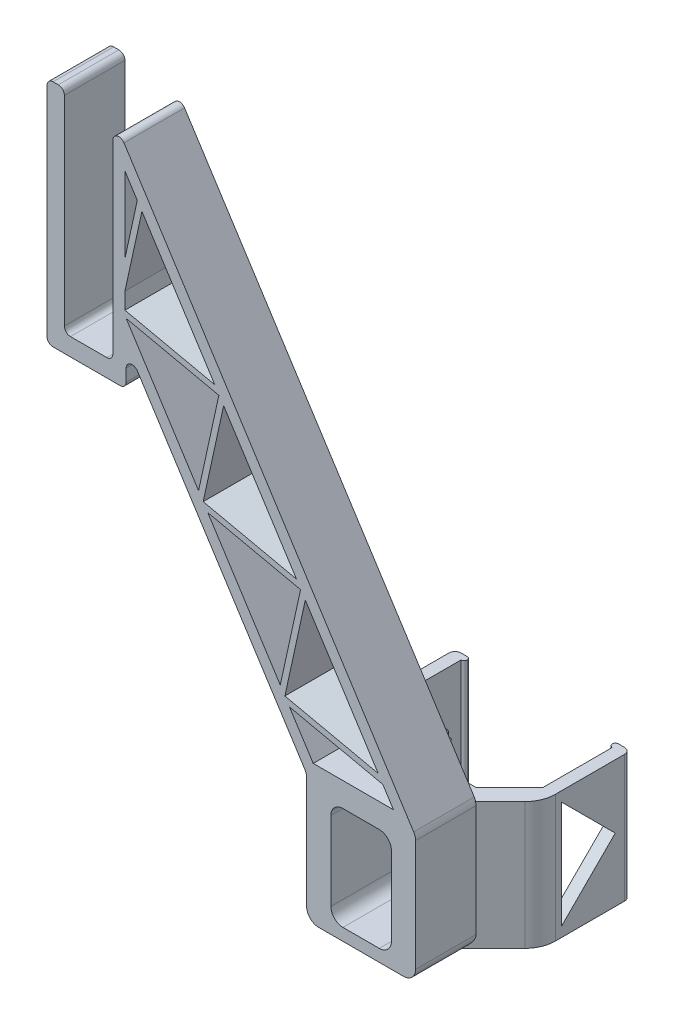
SolidWorks part; units mm, degrees
ref_plane "Front Plane" through (0, 0, 0) normal (0, 0, 1) x (1, 0, 0)
ref_plane "Top Plane" through (0, 0, 0) normal (0, 1, 0) x (1, 0, 0)
ref_plane "Right Plane" through (0, 0, 0) normal (1, 0, 0) x (0, 0, -1)
sketch "Sketch3" plane through (0, 0, 0) normal (0, 1, 0) x (1, 0, 0)
  line L0 (0, 0) -> (14, 0)
  line L1 (14, 0) -> (19.5, 5.5)
  line L2 (19.5, 5.5) -> (19.5, 18)
  line L3 (19.5, 18) -> (21.5, 18)
  line L4 (21.5, 18) -> (21.5, -2)
  line L5 (21.5, -2) -> (-7.5, -2)
  line L6 (-7.5, -2) -> (-7.5, 18)
  line L7 (-7.5, 18) -> (-5.5, 18)
  line L8 (-5.5, 18) -> (-5.5, 5.5)
  line L9 (-5.5, 5.5) -> (0, 0)
  line L10 (7, 0) -> (7, -2)
  line L11 (7, -2) -> (-2, -2)
  line L12 (7, -2) -> (16, -2)
  line L13 (16, -2) -> (21.5, 3.5)
  line L14 (-2, -2) -> (-7.5, 3.5)
  dimension "D1" = 135
  dimension "D2" = 135
  dimension "D3" = 14
  dimension "D4" = 12.5
  dimension "D5" = 12.5
  dimension "D6" = 2
  dimension "D7" = 2
  dimension "D8" = 2
  dimension "D9" = 20
  dimension "D10" = 20
  dimension "D11" = 135
  dimension "D12" = 135
  dimension "D13" = 9
  dimension "D14" = 9
extrude "Boss-Extrude2" add sketch "Sketch3" along normal blind 21 contours L10 L0 L9 L8 L7 L6 L5 | L0 L10 L5 L4 L3 L2 L1 region at (3.5, 0, 0.247) region at (10.5, 0, 0.247)
fillet "Fillet1" radius 5 2 edges at (21.5, 10.5, -3.5) (-7.5, 10.5, -3.5)
sketch "Sketch4" plane through (0, 21, 0) normal (0, 1, 0) x (1, 0, 0)
  line L0 (-5.5, 18) -> (-5.5, 5.5) construction
  circle A0 centre (-5.5, 17.5) radius 0.5
  dimension "D1" = 1
  dimension "D2" = 0.5
extrude "Boss-Extrude3" add sketch "Sketch4" against normal blind 21
sketch "Sketch5" plane through (0, 21, 0) normal (0, 1, 0) x (1, 0, 0)
  line L0 (19.5, 5.5) -> (19.5, 18) construction
  circle A0 centre (19.5, 17.5) radius 0.5
  dimension "D1" = 1
  dimension "D2" = 0.5
extrude "Boss-Extrude4" add sketch "Sketch5" against normal blind 21
fillet "Fillet2" radius 1 2 edges at (21.5, 10.5, -18) (-7.5, 10.5, -18)
sketch "Sketch6" plane through (0, 21, 0) normal (0, 1, 0) x (1, 0, 0)
  line L0 (16, -2) -> (-2, -2) construction
  line L1 (0, 0) -> (14, 0) construction
  line L2 (1.4514, 5) -> (1.4514, 0)
  line L3 (1.4514, 5) -> (4.4514, 5)
  line L4 (4.4514, 5) -> (4.4514, 0)
  line L7 (1.4514, 0) -> (1.4514, -2)
  line L8 (1.4514, -2) -> (4.4514, -2)
  line L9 (4.4514, 0) -> (4.4514, -2)
  dimension "D1" = 5
  dimension "D2" = 3
extrude "Boss-Extrude5" add sketch "Sketch6" along normal blind 1.5
fillet "Fillet3" radius 1 1 edges at (2.9514, 22.5, 2)
fillet "Fillet4" radius 1 1 edges at (2.9514, 22.5, -5)
sketch "Sketch7" plane through (1.4514, 0, 0) normal (-1, 0, 0) x (0, 0, 1)
  line L0 (-5, 21) -> (0, 21) construction
  circle A0 centre (-4.5, 21) radius 0.5
  dimension "D1" = 1
  dimension "D2" = 0.5
extrude "Boss-Extrude6" add sketch "Sketch7" against normal up to surface (3 mm away) up to face at (4.4514, 21.6663, -1.1429)
sketch "Sketch8" plane through (0, 0, 0) normal (0, -1, 0) x (1, 0, 0)
  line L0 (16, 2) -> (-2, 2) construction
  line L1 (1.4514, 2) -> (4.4514, 2)
  line L2 (1.4514, 2) -> (1.4514, -5)
  line L3 (1.4514, -5) -> (4.4514, -5)
  line L4 (4.4514, 2) -> (4.4514, -5)
extrude "Boss-Extrude7" add sketch "Sketch8" along normal blind 1.5
fillet "Fillet5" radius 1 2 edges at (2.9514, -1.5, -5) (2.9514, -1.5, 2)
sketch "Sketch9" plane through (4.4514, 0, 0) normal (1, 0, 0) x (0, 0, -1)
  line L0 (5, 0) -> (0, 0) construction
  circle A0 centre (4.5, 0) radius 0.5
  dimension "D1" = 1
  dimension "D2" = 0.5
extrude "Boss-Extrude8" add sketch "Sketch9" against normal up to surface (3 mm away) up to face at (1.4514, -0.6663, -1.1429)
sketch "Sketch10" plane through (0, 0, 0) normal (0, 0, -1) x (-1, 0, 0)
  line L0 (-4.4514, 21) -> (-14, 21) construction
  line L1 (-2, 19) -> (-12, 19)
  line L2 (-2, 19) -> (-2, 2)
  line L3 (-2, 2) -> (-12, 2)
  line L4 (-12, 19) -> (-12, 2)
  line L5 (-4.4514, 0) -> (-14, 0) construction
  line L6 (-14, 21) -> (-14, 0) construction
  line L7 (0, 21) -> (0, 0) construction
  point P4 (-9.2257, 21)
  dimension "D1" = 2
  dimension "D2" = 2
  dimension "D3" = 2
  dimension "D4" = 2
extrude "Cut-Extrude1" cut sketch "Sketch10" against normal through all
sketch "Sketch11" plane through (-7.5, 0, 0) normal (-1, 0, 0) x (0, 0, 1)
  line L0 (-6.5711, 19.4) -> (-6.5711, 1.6048)
  line L1 (-6.5711, 1.6048) -> (-15.4687, 10.5024)
  line L2 (-15.4687, 10.5024) -> (-6.5711, 19.4)
  line L3 (-5.5711, 0) -> (-17, 0) construction
  line L4 (-5.5711, 21) -> (-17, 21) construction
  line L5 (-5.5711, 0) -> (-5.5711, 21) construction
  dimension "D1" = 90
  dimension "D2" = 1.6048
  dimension "D3" = 1.6
  dimension "D4" = 1
extrude "Cut-Extrude2" cut sketch "Sketch11" against normal through all
sketch "Sketch12" plane through (0, 0, 2) normal (0, 0, 1) x (1, 0, 0)
  line L1 (16, 21) -> (-2, 21)
  line L2 (16, 21) -> (16, 0)
  line L3 (16, 0) -> (-2, 0)
  line L4 (-2, 21) -> (-2, 0)
  line L5 (12, 19) -> (2, 19)
  line L6 (12, 19) -> (12, 2)
  line L7 (12, 2) -> (2, 2)
  line L8 (2, 19) -> (2, 2)
extrude "Boss-Extrude9" add sketch "Sketch12" along normal blind 10
sketch "Sketch13" plane through (0, 0, 12) normal (0, 0, 1) x (1, 0, 0)
  line L0 (16, 21) -> (-34, 99)
  line L1 (-2, 21) -> (-34, 70.9218)
  line L2 (-34, 70.9218) -> (-34, 99)
  line L4 (16, 21) -> (-2, 21) construction
  line L5 (16, 21) -> (-2, 21)
  line L6 (-0.9064, 23) -> (-32, 71.5077)
  line L7 (-32, 71.5077) -> (-32, 92.174)
  line L8 (12.3423, 23) -> (-32, 92.174)
  line L9 (12.3423, 23) -> (-0.9064, 23)
  dimension "D1" = 78
  dimension "D2" = 50
  dimension "D3" = 122.661
  dimension "D4" = 122.66
  dimension "D5" = 28.0782
  dimension "D6" = 2
extrude "Boss-Extrude10" add sketch "Sketch13" against normal blind 10
sketch "Sketch14" plane through (0, 0, 12) normal (0, 0, 1) x (1, 0, 0)
  line L0 (10.5854, 25.7408) -> (-4.8239, 29.1116)
  line L1 (12.3423, 23) -> (-32, 92.174) construction
  line L2 (-32, 71.5077) -> (-0.9064, 23) construction
  line L3 (-4.8239, 29.1116) -> (-6.7486, 29.5326)
  line L4 (10.7991, 26.7177) -> (-4.6102, 30.0885)
  line L5 (-4.6102, 30.0885) -> (-6.5349, 30.5095)
  line L6 (10.5854, 25.7408) -> (10.7991, 26.7177)
  line L7 (-6.5349, 30.5095) -> (-6.7486, 29.5326)
  dimension "D1" = 45
  dimension "D2" = 1
extrude "Boss-Extrude14" add sketch "Sketch14" against normal blind 10
sketch "Sketch16" plane through (0, 0, 12) normal (0, 0, 1) x (1, 0, 0)
  line L0 (-5.5871, 30.3022) -> (-2.2163, 45.7115)
  line L1 (9.8222, 26.9314) -> (-32, 92.174) construction
  line L2 (-2.2163, 45.7115) -> (-2.0256, 46.5834)
  line L3 (9.8222, 26.9314) -> (-5.5871, 30.3022) construction
  line L4 (-2.0256, 46.5834) -> (-1.7752, 47.7281)
  line L5 (-6.564, 30.5159) -> (-3.1932, 45.9252)
  line L6 (-3.1932, 45.9252) -> (-3.0025, 46.7971)
  line L7 (-3.0025, 46.7971) -> (-2.7521, 47.9418)
  line L8 (-5.5871, 30.3022) -> (-6.564, 30.5159)
  line L9 (-2.7521, 47.9418) -> (-1.7752, 47.7281)
  dimension "D1" = 90
  dimension "D2" = 1
extrude "Boss-Extrude15" add sketch "Sketch16" against normal blind 10
pattern_linear "LPattern1" count 3 spacing 25 along (-0.5397, 0.8419, 0) of "Boss-Extrude14", "Boss-Extrude15"
sketch "Sketch17" plane through (0, 0, 12) normal (0, 0, 1) x (1, 0, 0)
  line L0 (-34, 99) -> (-34, 70.9218) construction
  line L1 (-42, 64) -> (-44.8755, 64)
  line L2 (-42, 64) -> (-42, 99)
  line L3 (-42, 99) -> (-44.8755, 99)
  line L4 (-44.8755, 64) -> (-44.8755, 99)
  dimension "D1" = 8
  dimension "D2" = 35
  dimension "D3" = 0
extrude "Boss-Extrude16" add sketch "Sketch17" against normal blind 10 separate body
sketch "Sketch18" plane through (0, 0, 12) normal (0, 0, 1) x (1, 0, 0)
  line L0 (-34, 64) -> (-34, 71.0352)
  line L1 (-34, 71.0352) -> (-31.8062, 71.2053)
  line L2 (-42, 64) -> (-44.8755, 64)
  line L3 (-44.8755, 64) -> (-44.8755, 61.0815)
  line L4 (-44.8755, 61.0815) -> (-34, 61.0815)
  line L5 (-31.8062, 71.2053) -> (-31.8062, 61.0815)
  line L9 (-42, 64) -> (-34, 64)
  line L10 (-34, 61.0815) -> (-31.8062, 61.0815)
extrude "Boss-Extrude17" add sketch "Sketch18" against normal blind 10 contours L4 L10 L5 L1 L0 L9 L2 L3
fillet "Fillet6" radius 1 1 edges at (-31.8062, 67.4992, 7)
fillet "Fillet7" radius 1 5 edges at (-34, 99, 7) (-42, 99, 7) (-44.8755, 99, 7) (-44.8755, 61.0815, 7) (-31.8062, 61.0815, 7)
fillet "Fillet8" radius 1 2 edges at (-42, 64, 7) (-34, 64, 7)
fillet "Fillet9" radius 2 8 edges at (2, 19, 6) (2, 2, 6) (12, 2, 6) (12, 19, 6) (-2, 0, 7) (16, 0, 7) (16, 21, 7) (-2, 21, 7)
